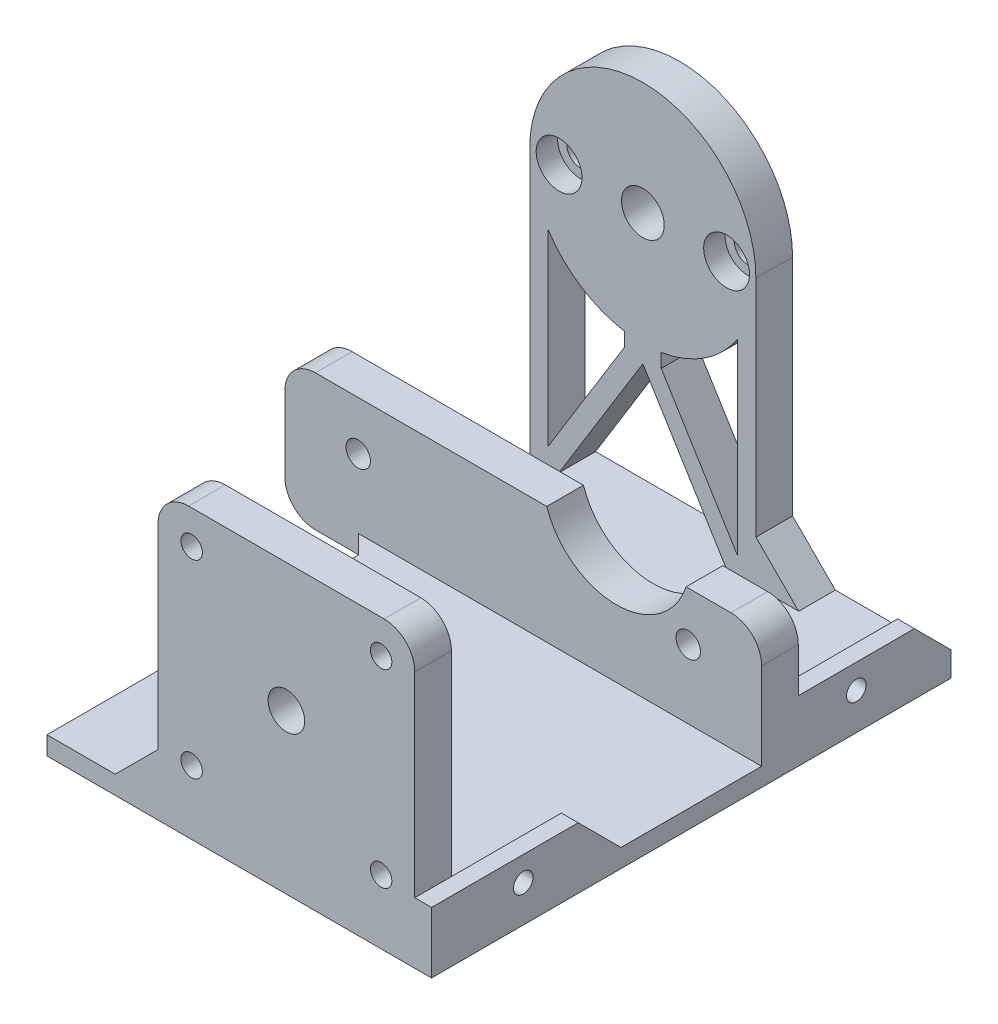
SolidWorks part; units mm, degrees
ref_plane "Front Plane" through (0, 0, 0) normal (0, 0, 1) x (1, 0, 0)
ref_plane "Top Plane" through (0, 0, 0) normal (0, 1, 0) x (1, 0, 0)
ref_plane "Right Plane" through (0, 0, 0) normal (1, 0, 0) x (0, 0, -1)
sketch "Sketch1" plane through (0, 0, 0) normal (0, 0, 1) x (1, 0, 0)
  circle A0 centre (0, 0) radius 3.5
  circle A1 centre (-13.7, 0) radius 2.25
  circle A2 centre (13.7, 0) radius 2.25
  circle A3 centre (0, 0) radius 18.5
  dimension "D3" = 4.5
  dimension "D4" = 7
  dimension "D5" = 37
  dimension "D1" = 13.7
  dimension "D2" = 13.7
extrude "Boss-Extrude1" add sketch "Sketch1" along normal blind 6
sketch "Sketch2" plane through (0, 0, 6) normal (0, 0, 1) x (1, 0, 0)
  circle A0 centre (-13.7, 0) radius 3.75
  circle A1 centre (13.7, 0) radius 3.75
  dimension "D1" = 7.5
extrude "Cut-Extrude1" cut sketch "Sketch2" against normal blind 3.5
sketch "Sketch3" plane through (0, 0, 6) normal (0, 0, 1) x (1, 0, 0)
  line L0 (-18.5, 0) -> (-18.5, -46.68)
  line L1 (18.5, 0) -> (18.5, -46.68)
  line L2 (18.5, -46.68) -> (-18.5, -46.68)
  line L3 (15.5, 0) -> (15.5, -43.68)
  line L4 (15.5, -43.68) -> (-15.5, -43.68)
  line L5 (-15.5, 0) -> (-15.5, -43.68)
  line L6 (-15.5, -43.68) -> (0, -18.5) construction
  line L7 (0, -18.5) -> (15.5, -43.68) construction
  line L8 (-15.5, -40.8186) -> (-1.7125, -18.4206)
  line L9 (0, 0) -> (0, -18.5) construction
  line L10 (0, -18.5) -> (0, -43.68) construction
  line L11 (-13.7386, -43.68) -> (0, -21.3614)
  line L12 (15.5, -40.8186) -> (1.7125, -18.4206)
  line L13 (13.7386, -43.68) -> (0, -21.3614)
  line L14 (-15.5, -10.0995) -> (-18.5, 0)
  line L15 (18.5, 0) -> (15.5, -10.0995)
  line L16 (-3, -20.5121) -> (-3, -18.2551)
  line L17 (3, -20.5121) -> (3, -18.2551)
  circle A0 centre (0, 0) radius 18.5 construction
  circle A1 centre (0, 0) radius 18.5
  circle M4 centre (0, 0) radius 18.5
  dimension "D1" = 46.68
  dimension "D3" = 1.5
  dimension "D4" = 1.5
  dimension "D5" = 3
  dimension "D2" = 3
extrude "Boss-Extrude2" add sketch "Sketch3" against normal blind 6 contours L5 L0 L2 L1 L3 L4 M4 | L13 L4 L3 L12 L8 L5 L11 M4 | L12 L17 M4 | L16 L8 M4 region at (-18.3051, -5.4374, 6) region at (-8.9095, -30.875, 6) region at (-2.5723, -19.0675, 6) region at (2.5723, -19.0675, 6)
sketch "Sketch4" plane through (0, 0, 0) normal (0, 0, 1) x (1, 0, 0)
  line L0 (13.7386, -43.68) -> (-13.7386, -43.68) construction
  line L1 (-18.5, -46.68) -> (44.43, -46.68)
  line L2 (-18.5, -46.68) -> (-18.5, -43.68)
  line L3 (-18.5, -43.68) -> (44.43, -43.68)
  line L4 (44.43, -46.68) -> (44.43, -43.68)
  dimension "D1" = 44.43
extrude "Boss-Extrude3" add sketch "Sketch4" along normal blind 85
ref_plane "Plane1" through (0, 0, 31) normal (0, 0, -1) x (-1, 0, 0)
sketch "Sketch6" plane through (0, 0, 31) normal (0, 0, -1) x (-1, 0, 0)
  line L0 (-44.43, -43.68) -> (-18.5, -43.68) construction
  line L1 (-44.43, -46.68) -> (-44.43, -43.68) construction
  line L7 (-44.43, -43.68) -> (33.57, -43.68)
  line L8 (-44.43, -43.68) -> (-44.43, -24.43)
  line L9 (-44.43, -24.43) -> (33.57, -24.43)
  line L10 (33.57, -43.68) -> (33.57, -24.43)
  circle A0 centre (-32.43, -32.43) radius 2
  circle A1 centre (21.57, -32.43) radius 2
  circle A2 centre (-20.68, -20.68) radius 12
  dimension "D2" = 4
  dimension "D3" = 4
  dimension "D10" = 24
  dimension "D1" = 11.25
  dimension "D4" = 66
  dimension "D5" = 12
  dimension "D6" = 12
  dimension "D7" = 8
  dimension "D8" = 23.75
  dimension "D9" = 3.75
extrude "Boss-Extrude5" add sketch "Sketch6" along normal blind 6 contours A2 L9 L8 L7 L10 A1 A0 region at (3.8616, -34.7235, 31)
sketch "Sketch5" plane through (0, 0, 85) normal (0, 0, 1) x (1, 0, 0)
  line L6 (44.43, -46.68) -> (44.43, -43.68) construction
  line L7 (44.43, -43.68) -> (-18.5, -43.68) construction
  line L8 (20.68, -20.68) -> (20.68, -5.18) construction
  line L9 (20.68, -20.68) -> (36.18, -20.68) construction
  line L10 (41.68, -43.68) -> (41.68, 0.32)
  line L11 (-0.32, -43.68) -> (-0.32, 0.32)
  line L12 (-0.32, 0.32) -> (41.68, 0.32)
  circle A0 centre (20.68, -20.68) radius 3
  circle A1 centre (36.18, -5.18) radius 1.75
  circle A2 centre (36.18, -36.18) radius 1.75
  circle A3 centre (5.18, -36.18) radius 1.75
  circle A4 centre (5.18, -5.18) radius 1.75
  line M11 (44.43, -43.68) -> (-18.5, -43.68)
  dimension "D3" = 6
  dimension "D6" = 3.5
  dimension "D1" = 23.75
  dimension "D2" = 23
  dimension "D4" = 15.5
  dimension "D5" = 15.5
  dimension "D7" = 21
  dimension "D8" = 21
extrude "Boss-Extrude4" add sketch "Sketch5" against normal blind 6 contours L12 L11 L10 A2 A1 A0 A3 A4 M11 region at (20.68, -43.0717, 85)
sketch "Sketch7" plane through (0, -46.68, 0) normal (0, -1, 0) x (1, 0, 0)
  line L7 (-18.5, 25) -> (-33.57, 25)
  line L8 (-18.5, 25) -> (-18.5, 31)
  line L9 (-18.5, 31) -> (-33.57, 31)
  line L10 (-33.57, 25) -> (-33.57, 31)
  line M6 (-18.5, 85) -> (-18.5, 0)
extrude "Boss-Extrude6" add sketch "Sketch7" against normal up to surface (3 mm away) contours L10 L7 L9 M6 region at (-26.035, -46.68, 28) up to face at (-26.035, -43.68, 28)
chamfer "Chamfer1" distance 3 angle 45 2 edges at (-18.5, -45.18, 25) (-18.5, -45.18, 31)
sketch "Sketch8" plane through (44.43, 0, 0) normal (1, 0, 0) x (0, 0, -1)
  line L1 (-6, -43.68) -> (-25, -43.68)
  line L2 (-6, -43.68) -> (-6, -36.68)
  line L3 (-6, -36.68) -> (-25, -36.68)
  line L4 (-25, -43.68) -> (-25, -36.68)
  line L5 (0, 0) -> (0, -43.68) construction
  line L7 (-79, -43.68) -> (-61, -43.68)
  line L8 (-79, -43.68) -> (-79, -36.68)
  line L9 (-79, -36.68) -> (-61, -36.68)
  line L10 (-61, -43.68) -> (-61, -36.68)
  line L11 (-79, -36.68) -> (-85, -36.68)
  line L12 (-79, -36.68) -> (-79, -43.68)
  line L13 (-79, -43.68) -> (-85, -43.68)
  line L14 (-85, -36.68) -> (-85, -43.68)
  circle A0 centre (-15.5, -40.68) radius 1.6
  circle A1 centre (-70, -40.68) radius 1.6
  line M12 (0, -43.68) -> (-25, -43.68)
  line M13 (-25, -43.68) -> (-25, -24.43)
  line M16 (-31, -43.68) -> (-85, -43.68)
  dimension "D2" = 3.2
  dimension "D5" = 3.2
  dimension "D1" = 3
  dimension "D3" = 9.5
  dimension "D4" = 70
  dimension "D6" = 7
  dimension "D7" = 7
  dimension "D8" = 18
extrude "Boss-Extrude7" add sketch "Sketch8" against normal blind 2.75 contours L11 L14 L8 M16 | L10 L9 L8 A1 M16 | L2 L3 A0 M13 M12 region at (44.43, -43.4775, 15.5) region at (44.43, -40.18, 78.8069) region at (44.43, -40.18, 82)
chamfer "Chamfer2" distance 7 angle 45 4 edges at (-0.32, -43.68, 82) (18.5, -43.68, 3) (43.055, -43.68, 6) (43.055, -43.68, 61)
fillet "Fillet1" radius 5 5 edges at (44.43, -24.43, 28) (-33.57, -46.68, 28) (-33.57, -24.43, 28) (41.68, 0.32, 82) (-0.32, 0.32, 82)
chamfer "Chamfer3" distance 3 angle 45 2 edges at (30.43, -32.43, 25) (-23.57, -32.43, 25)
